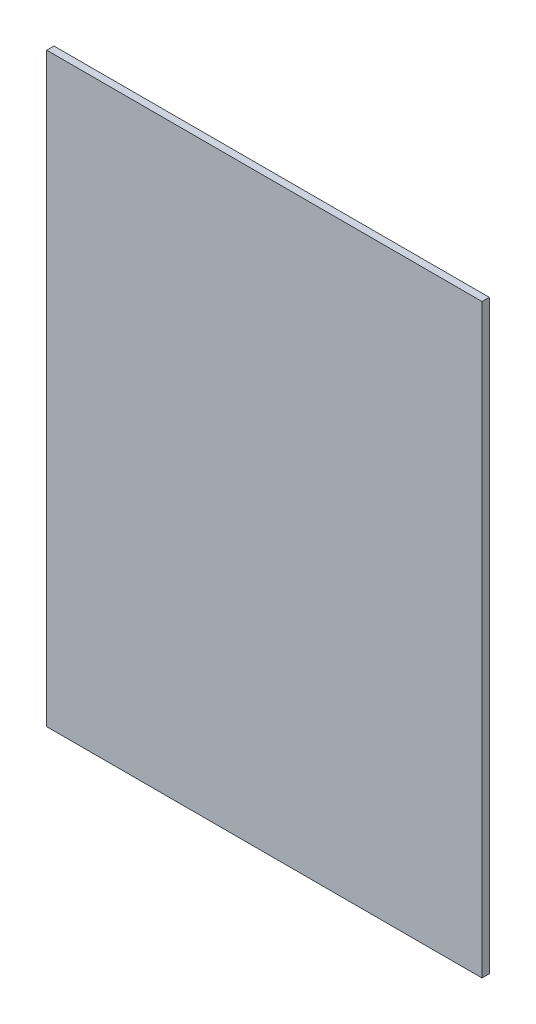
SolidWorks part; units mm, degrees
ref_plane "前视基准面" through (0, 0, 0) normal (0, 0, 1) x (1, 0, 0)
ref_plane "上视基准面" through (0, 0, 0) normal (0, 1, 0) x (1, 0, 0)
ref_plane "右视基准面" through (0, 0, 0) normal (1, 0, 0) x (0, 0, -1)
sketch "草图1" plane through (0, 0, 0) normal (0, 0, 1) x (1, 0, 0)
  line L1 (-60, 80.75) -> (60, 80.75)
  line L2 (-60, 80.75) -> (-60, -80.75)
  line L3 (-60, -80.75) -> (60, -80.75)
  line L4 (60, 80.75) -> (60, -80.75)
  line L5 (-60, 80.75) -> (60, -80.75) construction
  line L6 (-60, -80.75) -> (60, 80.75) construction
  point P0 (0, 0)
  dimension "D1" = 161.5
  dimension "D2" = 120
base flange "基体-法兰1" sketch "草图1" thickness 2 reverse thickness direction no parameters "D1"=1
sketch "折弯-线1" plane through (0, 0, 0) normal (0, 1, 0) x (1, 0, 0)
sketch "边界框1" plane through (0, 0, 0) normal (0, 1, 0) x (1, 0, 0)
sheet metal parameters "钣金6" thickness 2 parameters "D1"=1
flat pattern "平板型式6" [suppressed]
sketch "折弯-线2" plane through (0, 0, 0) normal (0, 1, 0) x (1, 0, 0)
sketch "边界框2" [suppressed] plane through (0, 0, 0) normal (0, 1, 0) x (1, 0, 0)
